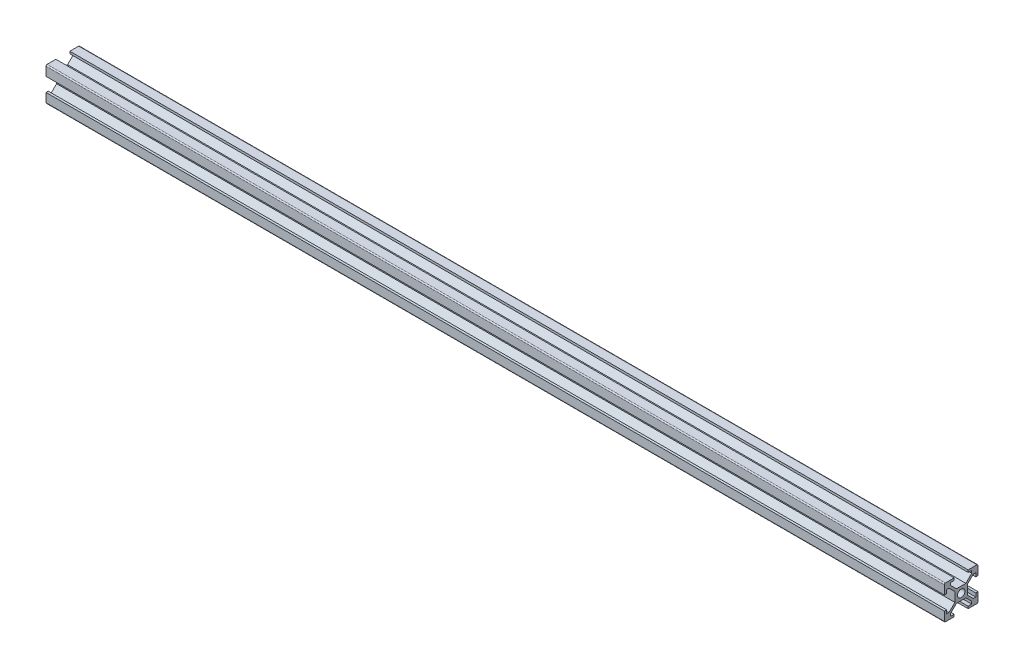
SolidWorks part; units mm, degrees
ref_plane "前视基准面" through (0, 0, 0) normal (0, 0, 1) x (1, 0, 0)
ref_plane "上视基准面" through (0, 0, 0) normal (0, 1, 0) x (1, 0, 0)
ref_plane "右视基准面" through (0, 0, 0) normal (1, 0, 0) x (0, 0, -1)
sketch "草图2" plane through (0, 0, 0) normal (1, 0, 0) x (0, 0, -1)
  line L0 (-3.1, 7.5) -> (3.1, 7.5)
  line L1 (-7, 7.5) -> (7, 7.5)
  line L2 (-7.5, 7) -> (-7.5, -7)
  line L3 (-7, -7.5) -> (7, -7.5)
  line L4 (7.5, 7) -> (7.5, -7)
  line L5 (-3.1, 7.5) -> (-3.1, 6.5)
  line L6 (-3.1, 6.5) -> (-4.7, 6.5)
  line L7 (-4.7, 6.5) -> (-4.7, 5.4071)
  line L8 (-4.7, 5.4071) -> (-2.0929, 2.8)
  line L9 (-2.0929, 2.8) -> (2.0929, 2.8)
  line L10 (2.0929, 2.8) -> (4.7, 5.4071)
  line L11 (4.7, 5.4071) -> (4.7, 6.5)
  line L12 (4.7, 6.5) -> (3.1, 6.5)
  line L13 (3.1, 6.5) -> (3.1, 7.5)
  line L14 (-7.5, -7.5) -> (7.5, 7.5) construction
  line L15 (7.5, -7.5) -> (-7.5, 7.5) construction
  line L17 (-2.8, 2.8) -> (2.8, 2.8)
  line L18 (-2.8, 2.8) -> (-2.8, -2.8)
  line L19 (-2.8, -2.8) -> (2.8, -2.8)
  line L20 (2.8, 2.8) -> (2.8, -2.8)
  line L21 (-2.8, 2.8) -> (2.8, -2.8) construction
  line L22 (-2.8, -2.8) -> (2.8, 2.8) construction
  line L52 (7.5, 3.1) -> (7.5, -3.1)
  line L53 (6.5, -3.1) -> (7.5, -3.1)
  line L54 (6.5, -4.7) -> (6.5, -3.1)
  line L55 (5.4071, -4.7) -> (6.5, -4.7)
  line L56 (2.8, -2.0929) -> (5.4071, -4.7)
  line L57 (2.8, 2.0929) -> (2.8, -2.0929)
  line L58 (5.4071, 4.7) -> (2.8, 2.0929)
  line L59 (6.5, 4.7) -> (5.4071, 4.7)
  line L60 (6.5, 3.1) -> (6.5, 4.7)
  line L61 (7.5, 3.1) -> (6.5, 3.1)
  line L62 (3.1, -7.5) -> (-3.1, -7.5)
  line L63 (-3.1, -6.5) -> (-3.1, -7.5)
  line L64 (-4.7, -6.5) -> (-3.1, -6.5)
  line L65 (-4.7, -5.4071) -> (-4.7, -6.5)
  line L66 (-2.0929, -2.8) -> (-4.7, -5.4071)
  line L67 (2.0929, -2.8) -> (-2.0929, -2.8)
  line L68 (4.7, -5.4071) -> (2.0929, -2.8)
  line L69 (4.7, -6.5) -> (4.7, -5.4071)
  line L70 (3.1, -6.5) -> (4.7, -6.5)
  line L71 (3.1, -7.5) -> (3.1, -6.5)
  line L72 (-7.5, -3.1) -> (-7.5, 3.1)
  line L73 (-6.5, 3.1) -> (-7.5, 3.1)
  line L74 (-6.5, 4.7) -> (-6.5, 3.1)
  line L75 (-5.4071, 4.7) -> (-6.5, 4.7)
  line L76 (-2.8, 2.0929) -> (-5.4071, 4.7)
  line L77 (-2.8, -2.0929) -> (-2.8, 2.0929)
  line L78 (-5.4071, -4.7) -> (-2.8, -2.0929)
  line L79 (-6.5, -4.7) -> (-5.4071, -4.7)
  line L80 (-6.5, -3.1) -> (-6.5, -4.7)
  line L81 (-7.5, -3.1) -> (-6.5, -3.1)
  line L82 (0, 0) -> (2.0929, 2.8) construction
  line L83 (0, 0) -> (2.8, -2.0929) construction
  circle A0 centre (0, 0) radius 1.65
  circle A1 centre (-7, 7) radius 0.5 construction
  circle A2 centre (-7, -7) radius 0.5 construction
  circle A3 centre (7, -7) radius 0.5 construction
  circle A4 centre (7, 7) radius 0.5 construction
  arc A5 (7, 7.5) -> (7.5, 7) centre (7, 7) cw
  arc A6 (7, -7.5) -> (7.5, -7) centre (7, -7) ccw
  arc A7 (-7.5, -7) -> (-7, -7.5) centre (-7, -7) ccw
  arc A8 (-7, 7.5) -> (-7.5, 7) centre (-7, 7) ccw
  point P16 (0, 0)
  point P28 (0, 0)
  point P50 (0, 7.5)
  point P52 (7.5, 0)
  point P62 (-7, -7)
  point P65 (7, -7)
  point P68 (7, 7)
  dimension "D3" = 3.3
  dimension "D12" = 1
  dimension "D13" = 1
  dimension "D14" = 1
  dimension "D15" = 1
  dimension "D16" = 0.5
  dimension "D1" = 15
  dimension "D2" = 6.2
  dimension "D4" = 5.6
  dimension "D5" = 9.4
  dimension "D6" = 0.5
  dimension "D7" = 0.5
  dimension "D8" = 4.7
  dimension "D9" = 1
  dimension "D10" = 4
  dimension "D11" = 90
extrude "凸台-拉伸1" add sketch "草图2" along normal blind 400 contours L2 A7 L3 A6 L4 A5 L1 A8
extrude "切除-拉伸2" cut sketch "草图2<4>" against normal through all and the other way through all contours L3 L71 L70 L69 L68 L19 L66 L65 L64 L63 | L2 L81 L80 L79 L78 L18 L76 L75 L74 L73 | L12 L13 L0 L5 L6 L7 L8 L9 L10 L11 | L4 L61 L60 L59 L58 L20 L56 L55 L54 L53 | A0 region at (0, 5.2713, 0) region at (0, 0, 5.2713) region at (0, 0, -5.2713) region at (0, -5.2713, 0) region at (0, 0, 0)
sketch "草图2<4>" plane through (0, 0, 0) normal (1, 0, 0) x (0, 0, -1) same geometry as "草图2"
